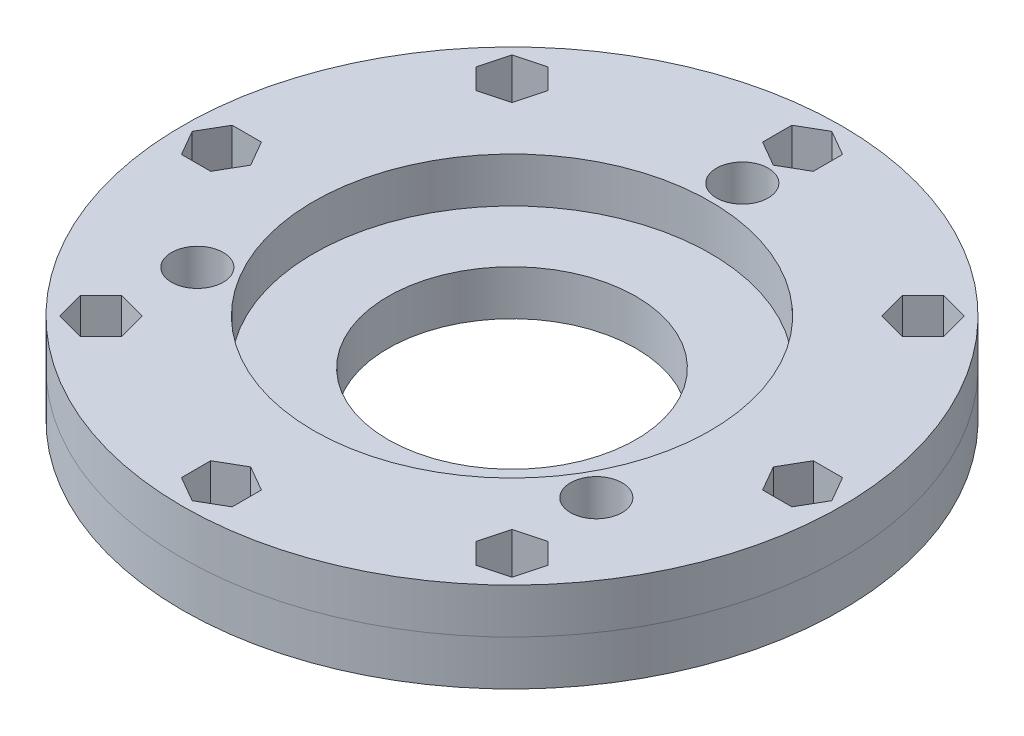
SolidWorks part; units mm, degrees
ref_plane "Front Plane" through (0, 0, 0) normal (0, 0, 1) x (1, 0, 0)
ref_plane "Top Plane" through (0, 0, 0) normal (0, 1, 0) x (1, 0, 0)
ref_plane "Right Plane" through (0, 0, 0) normal (1, 0, 0) x (0, 0, -1)
sketch "Sketch1" plane through (0, 0, 0) normal (0, 1, 0) x (1, 0, 0)
  circle A0 centre (0, 0) radius 46.5
  circle A1 centre (0, 0) radius 32.5 construction
  circle A2 centre (0, 32.5) radius 2.25
  circle A3 centre (28.1458, -16.25) radius 2.25
  circle A4 centre (-28.1458, -16.25) radius 2.25
  circle A5 centre (0, 0) radius 17.5
  point P13 (0, 0)
  dimension "D1" = 93
  dimension "D2" = 65
  dimension "D3" = 4.5
  dimension "D5" = 35
  dimension "D4" = 3
extrude "Boss-Extrude1" add sketch "Sketch1" along normal blind 12.7
sketch "Sketch2" plane through (0, 12.7, 0) normal (0, 1, 0) x (1, 0, 0)
  circle A0 centre (0, 0) radius 28
  dimension "D1" = 56
extrude "Cut-Extrude1" cut sketch "Sketch2" against normal blind 6.35
sketch "Sketch3" plane through (0, 12.7, 0) normal (0, 1, 0) x (1, 0, 0)
  line L0 (0, 41) -> (0, 0) construction
  circle A0 centre (0, 0) radius 41 construction
  circle A1 centre (0, 41) radius 2.5
  circle A2 centre (28.9914, 28.9914) radius 2.5
  circle A3 centre (41, 0) radius 2.5
  circle A4 centre (28.9914, -28.9914) radius 2.5
  circle A5 centre (0, -41) radius 2.5
  circle A6 centre (-28.9914, -28.9914) radius 2.5
  circle A7 centre (-41, 0) radius 2.5
  circle A8 centre (-28.9914, 28.9914) radius 2.5
  point P21 (0, 0)
  dimension "D1" = 82
  dimension "D2" = 5
  dimension "D3" = 8
extrude "Cut-Extrude2" cut sketch "Sketch3" against normal blind 6.35
sketch "Sketch4" plane through (0, 12.7, 0) normal (0, 1, 0) x (1, 0, 0)
  line L0 (0, 45.1281) -> (-3.575, 43.064)
  line L1 (-3.575, 43.064) -> (-3.575, 38.936)
  line L2 (-3.575, 38.936) -> (0, 36.8719)
  line L3 (0, 36.8719) -> (3.575, 38.936)
  line L4 (3.575, 38.936) -> (3.575, 43.064)
  line L5 (3.575, 43.064) -> (0, 45.1281)
  line L6 (0, 45.1281) -> (0, 36.8719) construction
  line L7 (32.9788, 27.923) -> (31.9104, 31.9104)
  line L8 (31.9104, 31.9104) -> (27.923, 32.9788)
  line L9 (27.923, 32.9788) -> (25.004, 30.0598)
  line L10 (25.004, 30.0598) -> (26.0724, 26.0724)
  line L11 (26.0724, 26.0724) -> (30.0598, 25.004)
  line L12 (30.0598, 25.004) -> (32.9788, 27.923)
  line L13 (43.064, -3.575) -> (45.1281, 0)
  line L14 (45.1281, 0) -> (43.064, 3.575)
  line L15 (43.064, 3.575) -> (38.936, 3.575)
  line L16 (38.936, 3.575) -> (36.8719, 0)
  line L17 (36.8719, 0) -> (38.936, -3.575)
  line L18 (38.936, -3.575) -> (43.064, -3.575)
  line L19 (27.923, -32.9788) -> (31.9104, -31.9104)
  line L20 (31.9104, -31.9104) -> (32.9788, -27.923)
  line L21 (32.9788, -27.923) -> (30.0598, -25.004)
  line L22 (30.0598, -25.004) -> (26.0724, -26.0724)
  line L23 (26.0724, -26.0724) -> (25.004, -30.0598)
  line L24 (25.004, -30.0598) -> (27.923, -32.9788)
  line L25 (-3.575, -43.064) -> (0, -45.1281)
  line L26 (0, -45.1281) -> (3.575, -43.064)
  line L27 (3.575, -43.064) -> (3.575, -38.936)
  line L28 (3.575, -38.936) -> (0, -36.8719)
  line L29 (0, -36.8719) -> (-3.575, -38.936)
  line L30 (-3.575, -38.936) -> (-3.575, -43.064)
  line L31 (-32.9788, -27.923) -> (-31.9104, -31.9104)
  line L32 (-31.9104, -31.9104) -> (-27.923, -32.9788)
  line L33 (-27.923, -32.9788) -> (-25.004, -30.0598)
  line L34 (-25.004, -30.0598) -> (-26.0724, -26.0724)
  line L35 (-26.0724, -26.0724) -> (-30.0598, -25.004)
  line L36 (-30.0598, -25.004) -> (-32.9788, -27.923)
  line L37 (-43.064, 3.575) -> (-45.1281, 0)
  line L38 (-45.1281, 0) -> (-43.064, -3.575)
  line L39 (-43.064, -3.575) -> (-38.936, -3.575)
  line L40 (-38.936, -3.575) -> (-36.8719, 0)
  line L41 (-36.8719, 0) -> (-38.936, 3.575)
  line L42 (-38.936, 3.575) -> (-43.064, 3.575)
  line L43 (-27.923, 32.9788) -> (-31.9104, 31.9104)
  line L44 (-31.9104, 31.9104) -> (-32.9788, 27.923)
  line L45 (-32.9788, 27.923) -> (-30.0598, 25.004)
  line L46 (-30.0598, 25.004) -> (-26.0724, 26.0724)
  line L47 (-26.0724, 26.0724) -> (-25.004, 30.0598)
  line L48 (-25.004, 30.0598) -> (-27.923, 32.9788)
  line L49 (-30.0598, 25.004) -> (-27.923, 32.9788) construction
  circle A0 centre (0, 32.5) radius 3.65
  circle A1 centre (28.1458, -16.25) radius 3.65
  circle A2 centre (-28.1458, -16.25) radius 3.65
  circle A3 centre (-28.1458, -16.25) radius 2.25 construction
  circle A4 centre (0, 41) radius 2.5 construction
  circle A5 centre (0, 41) radius 2.5 construction
  circle A6 centre (-28.9914, 28.9914) radius 2.5 construction
  circle A7 centre (-28.9914, 28.9914) radius 2.5 construction
  point P9 (0, 0)
  point P64 (0, 0)
  dimension "D1" = 3
  dimension "8" = 7.3
  dimension "7.15" = 7.15
  dimension "D3" = 120
  dimension "D4" = 120
  dimension "D5" = 8
extrude "Cut-Extrude3" cut sketch "Sketch4" against normal blind 6.35
sketch "Sketch5" plane through (0, 12.7, 0) normal (0, 1, 0) x (1, 0, 0)
  line L2 (0, 36.8719) -> (0, 45.1281) construction
  circle A0 centre (0, 41) radius 2.5 construction
  circle A1 centre (0, 32.5) radius 2.25 construction
  circle A2 centre (0, 32.5) radius 2.25 construction
  dimension "D1" = 5
split "Split1" bodies to split 105 resulting bodies 108 109 split by face at (0, 6.35, 17.5)
